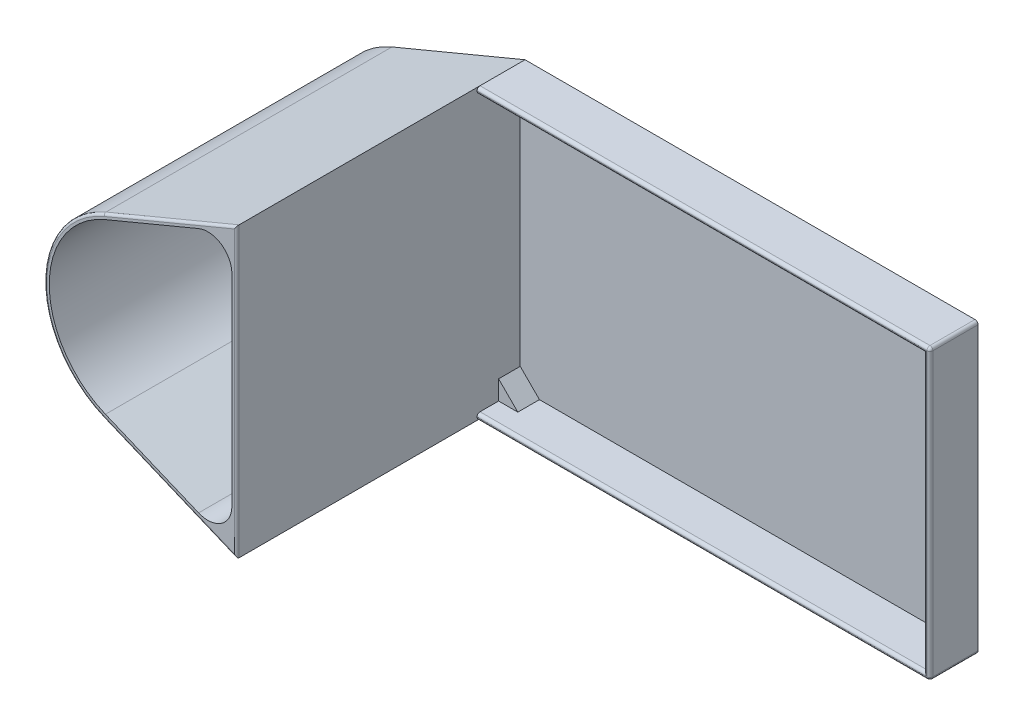
SolidWorks part; units mm, degrees
ref_plane "Płaszczyzna przednia" through (0, 0, 0) normal (0, 0, 1) x (1, 0, 0)
ref_plane "Płaszczyzna górna" through (0, 0, 0) normal (0, 1, 0) x (1, 0, 0)
ref_plane "Płaszczyzna prawa" through (0, 0, 0) normal (1, 0, 0) x (0, 0, -1)
sketch "Szkic1" plane through (0, 0, 0) normal (0, 0, 1) x (1, 0, 0)
  line L0 (47.75, 34.3887) -> (47.75, -37.2088) construction
  line L1 (-47.5, 30) -> (47.75, 30)
  line L2 (-47.5, 30) -> (-47.5, -30)
  line L3 (-47.5, -30) -> (47.75, -30)
  line L4 (47.75, 30) -> (47.75, -30)
  line L5 (-47.5, 30) -> (47.75, -30) construction
  line L6 (-47.5, -30) -> (47.75, 30) construction
  point P0 (0, 0)
  point P8 (0.125, 0)
  dimension "D1" = 60
  dimension "D2" = 47.5
  dimension "D3" = 47.75
  dimension "D4" = 0.125
extrude "Dodanie-wyciągnięcie1" add sketch "Szkic1" along normal blind 10
sketch "Szkic2" plane through (0, 0, 10) normal (0, 0, 1) x (1, 0, 0)
  line L1 (-46.5, 28.75) -> (46.5, 28.75)
  line L2 (-46.5, 28.75) -> (-46.5, -28.75)
  line L3 (-46.5, -28.75) -> (46.5, -28.75)
  line L4 (46.5, 28.75) -> (46.5, -28.75)
  line L5 (-46.5, 28.75) -> (46.5, -28.75) construction
  line L6 (-46.5, -28.75) -> (46.5, 28.75) construction
  point P0 (0, 0)
  dimension "D1" = 93
  dimension "D2" = 57.5
extrude "Wytnij-wyciągnięcie1" cut sketch "Szkic2" against normal blind 9
sketch "Szkic4" plane through (0, 0, 0) normal (0, 0, 1) x (1, 0, 0)
  line L0 (-46.5, -30) -> (-74.1923, -18.4615)
  line L1 (-46.5, 30) -> (-74.1923, 18.4615)
  line L2 (-47.5, -28.5) -> (-73.8077, -17.5385)
  line L3 (-46.5, -30) -> (-46.5, 30)
  line L4 (-47.5, 28.5) -> (-73.8077, 17.5385)
  line L5 (-47.5, -28.5) -> (-47.5, 28.5)
  line L6 (-46.5, -30) -> (-46.5, 30) construction
  line L7 (-46.5, 28.75) -> (-46.5, -28.75) construction
  line L8 (-47.5, -30) -> (47.75, -30) construction
  line L9 (47.75, 30) -> (-47.5, 30) construction
  arc A1 (-74.1923, 18.4615) -> (-74.1923, -18.4615) centre (-66.5, 0) ccw
  arc A2 (-73.8077, 17.5385) -> (-73.8077, -17.5385) centre (-66.5, 0) ccw
  dimension "D1" = 40
  dimension "D2" = 1
extrude "Dodanie-wyciągnięcie3" add sketch "Szkic4" along normal blind 60
sketch "Szkic6" plane through (0, 0, 10) normal (0, 0, 1) x (1, 0, 0)
  line L0 (-46.5, -30) -> (-47.5, -29.5833)
  line L1 (-47.5, -29.5833) -> (-47.5, -30)
  line L2 (-47.5, -30) -> (-46.5, -30)
  line L3 (-46.5, 30) -> (-47.5, 29.5833)
  line L4 (-47.5, 29.5833) -> (-47.5, 30)
  line L5 (-47.5, 30) -> (-46.5, 30)
extrude "Wytnij-wyciągnięcie2" cut sketch "Szkic6" against normal up to next
sketch "Szkic5" plane through (0, 0, 0) normal (0, 0, -1) x (-1, 0, 0)
  line L0 (73.8077, -17.5385) -> (47.5, -28.5) construction
  line L1 (47.5, 28.5) -> (73.8077, 17.5385) construction
  line L2 (47.5, -28.5) -> (47.5, 28.5) construction
  line L3 (73.8077, -17.5385) -> (47.5, -28.5)
  line L4 (47.5, 28.5) -> (73.8077, 17.5385)
  line L5 (47.5, -28.5) -> (47.5, 28.5)
  arc A0 (73.8077, -17.5385) -> (73.8077, 17.5385) centre (66.5, 0) ccw construction
  arc A1 (73.8077, -17.5385) -> (73.8077, 17.5385) centre (66.5, 0) ccw
extrude "Dodanie-wyciągnięcie4" add sketch "Szkic5" against normal blind 1
fillet "Zaokrąglenie1" radius 0.63 8 edges at (47.75, 30, 5) (47.75, -30, 5) (0.625, 30, 10) (47.75, 0, 10) (0.625, -30, 10) (46.5, 0, 10) (0, 28.75, 10) (0, -28.75, 10)
fillet "Zaokrąglenie2" radius 5 2 edges at (-47.5, 28.5, 30.5) (-47.5, -28.5, 30.5)
fillet "Zaokrąglenie3" radius 0.5 4 edges at (-60.3462, 24.2308, 60) (-86.5, 0, 60) (-46.5, 0, 60) (-60.3462, -24.2308, 60)
sketch "Szkic3" plane through (0, 0, 1) normal (0, 0, 1) x (1, 0, 0)
  line L0 (46.5, -28.75) -> (46.5, -24.75)
  line L1 (46.5, -28.75) -> (46.5, 28.75) construction
  line L2 (46.5, -24.75) -> (42.5, -28.75)
  line L3 (-46.5, -28.75) -> (46.5, -28.75) construction
  line L4 (42.5, -28.75) -> (46.5, -28.75)
  line L5 (0, -33) -> (0, 33) construction
  line L6 (-42.5, -28.75) -> (-46.5, -28.75)
  line L7 (-46.5, -24.75) -> (-42.5, -28.75)
  line L8 (-46.5, -28.75) -> (-46.5, -24.75)
  line L9 (33, 0) -> (-33, 0) construction
  line L10 (-46.5, 28.75) -> (-46.5, 24.75)
  line L11 (-46.5, 24.75) -> (-42.5, 28.75)
  line L12 (-42.5, 28.75) -> (-46.5, 28.75)
  line L13 (42.5, 28.75) -> (46.5, 28.75)
  line L14 (46.5, 24.75) -> (42.5, 28.75)
  line L15 (46.5, 28.75) -> (46.5, 24.75)
  dimension "D1" = 4
  dimension "D2" = 4
extrude "Dodanie-wyciągnięcie2" add sketch "Szkic3" along normal blind 4.5
fillet "Zaokrąglenie4" radius 4 6 edges at (-49.7265, -25.1603, 1) (-47.5, 0, 1) (-49.7265, 25.1603, 1) (-64.1154, 21.5769, 1) (-85.5, 0, 1) (-64.1154, -21.5769, 1)
